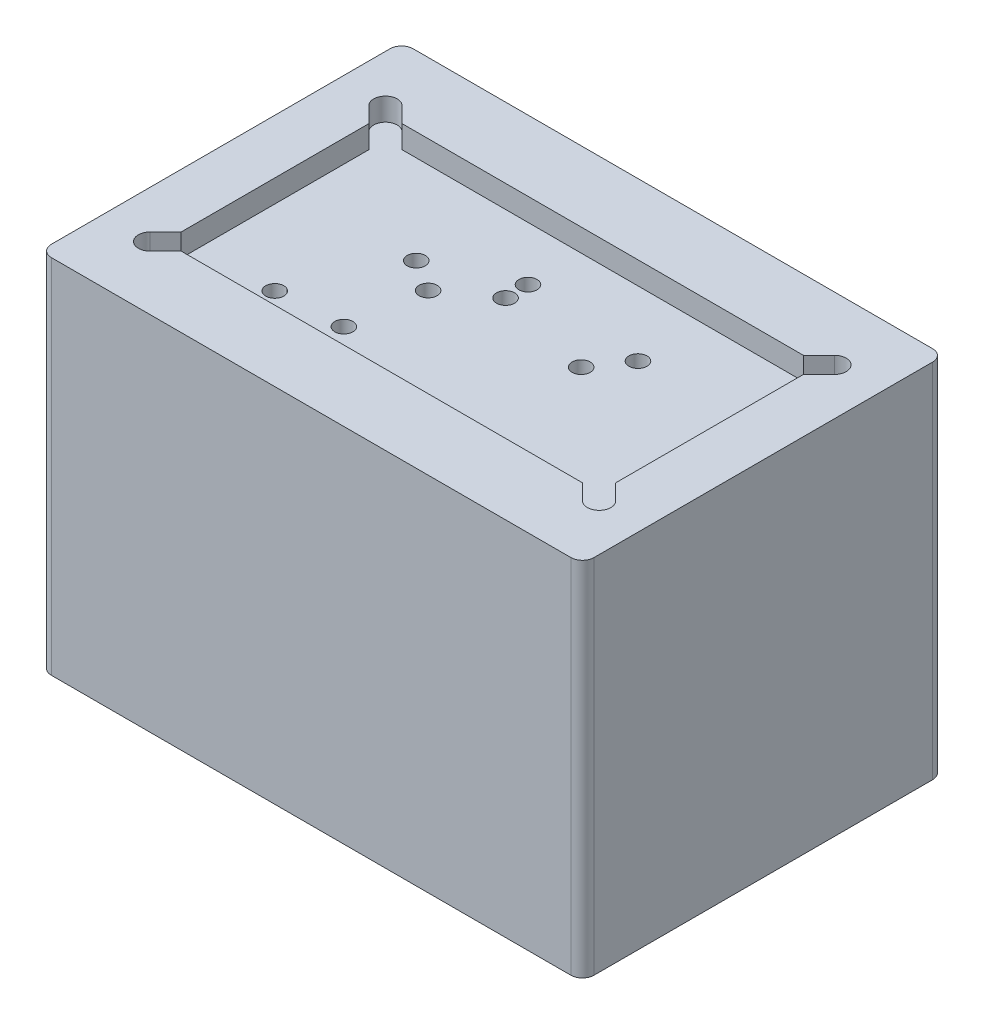
SolidWorks part; units mm, degrees
ref_plane "Front" through (0, 0, 0) normal (0, 0, 1) x (1, 0, 0)
ref_plane "Top" through (0, 0, 0) normal (0, 1, 0) x (1, 0, 0)
ref_plane "Right" through (0, 0, 0) normal (1, 0, 0) x (0, 0, -1)
sketch "Sketch1" plane through (0, 0, 0) normal (0, 1, 0) x (1, 0, 0)
  line L0 (-19.05, -12.7) -> (19.05, 12.7) construction
  line L1 (-19.05, 12.7) -> (19.05, 12.7)
  line L2 (-19.05, 12.7) -> (-19.05, -12.7)
  line L3 (-19.05, -12.7) -> (19.05, -12.7)
  line L4 (19.05, 12.7) -> (19.05, -12.7)
  point P4 (0, 0)
  dimension "D1" = 38.1
  dimension "D2" = 25.4
extrude "Boss-Extrude1" add sketch "Sketch1" along normal blind 25.4
sketch "Sketch3" plane through (0, 0, 0) normal (0, -1, 0) x (1, 0, 0)
  line L0 (-14.986, -7.5057) -> (15.014, -7.5057)
  line L1 (15.014, -7.5057) -> (15.014, 7.4943)
  line L2 (15.014, 7.4943) -> (-14.986, 7.4943)
  line L3 (-14.986, 7.4943) -> (-14.986, -7.5057)
  arc A0 (15.014, -7.5057) -> (15.014, -7.4993) centre (15.014, -7.5025) ccw
  arc A1 (-14.986, -7.5057) -> (-14.986, -7.512) centre (-14.986, -7.5089) ccw
  arc A2 (15.014, 7.4943) -> (15.0076, 7.4943) centre (15.0108, 7.4943) ccw
  arc A3 (15.014, -7.5057) -> (15.0203, -7.5057) centre (15.0172, -7.5057) ccw
  arc A4 (-14.986, 7.4943) -> (-14.986, 7.4879) centre (-14.986, 7.4911) ccw
  arc A5 (15.014, 7.4943) -> (15.014, 7.5006) centre (15.014, 7.4975) ccw
  arc A6 (-14.986, -7.5057) -> (-14.9796, -7.5057) centre (-14.9828, -7.5057) ccw
  arc A7 (-14.986, 7.4943) -> (-14.9923, 7.4943) centre (-14.9892, 7.4943) ccw
  circle A8 centre (-13.081, 5.5753) radius 1.1303
  circle A9 centre (13.1064, -5.6007) radius 1.1303
  circle A10 centre (-6.8326, -1.5113) radius 0.3175
  circle A11 centre (-9.9568, 5.2959) radius 0.3175
  circle A12 centre (-4.5974, -0.1143) radius 0.3175
  circle A13 centre (5.4356, -0.8255) radius 0.3175
  circle A14 centre (7.0612, -3.1877) radius 0.3175
  circle A15 centre (-1.4224, -2.3749) radius 0.3175
  circle A16 centre (-5.3594, 5.0419) radius 0.3175
  circle A17 centre (-1.4478, -3.9751) radius 0.3175
sketch "Sketch4" plane through (0, 25.4, 0) normal (0, 1, 0) x (1, 0, 0)
  circle A0 centre (-9.9568, -5.2959) radius 0.635
  circle A1 centre (-5.3594, -5.0419) radius 0.635
  circle A2 centre (-4.5974, 0.1143) radius 0.635
  circle A3 centre (-6.8326, 1.5113) radius 0.635
  circle A4 centre (-1.4478, 3.9751) radius 0.635
  circle A5 centre (-1.4224, 2.3749) radius 0.635
  circle A6 centre (5.4356, 0.8255) radius 0.635
  circle A7 centre (7.0612, 3.1877) radius 0.635
  circle A8 centre (5.4356, 0.8255) radius 0.3175 construction
  circle A9 centre (-9.9568, -5.2959) radius 0.3175 construction
  circle A10 centre (-5.3594, -5.0419) radius 0.3175 construction
  circle A11 centre (-4.5974, 0.1143) radius 0.3175 construction
  circle A12 centre (-6.8326, 1.5113) radius 0.3175 construction
  circle A13 centre (-1.4478, 3.9751) radius 0.3175 construction
  circle A14 centre (-1.4224, 2.3749) radius 0.3175 construction
  circle A15 centre (7.0612, 3.1877) radius 0.3175 construction
  dimension "D1" = 1.27
extrude "Cut-Extrude1" cut sketch "Sketch4" against normal through all
sketch "Sketch5" plane through (0, 25.4, 0) normal (0, 1, 0) x (1, 0, 0)
  line L4 (-15.1643, 8.8514) -> (-14.0726, 7.7597)
  line L5 (-16.3317, 7.684) -> (-15.24, 6.5923)
  line L6 (15.1923, 8.8514) -> (14.1006, 7.7597)
  line L7 (16.3597, 7.684) -> (15.268, 6.5923)
  line L8 (-15.24, 7.7597) -> (-15.24, -7.7483)
  line L9 (-15.24, -7.7483) -> (15.268, -7.7483)
  line L10 (15.268, -7.7483) -> (15.268, 7.7597)
  line L11 (15.268, 7.7597) -> (-15.24, 7.7597)
  line L12 (-15.24, 6.5923) -> (-15.24, -6.5809)
  line L13 (-14.0726, -7.7483) -> (14.1006, -7.7483)
  line L14 (15.268, -6.5809) -> (15.268, 6.5923)
  line L15 (14.1006, 7.7597) -> (-14.0726, 7.7597)
  line L16 (15.1923, -8.84) -> (14.1006, -7.7483)
  line L17 (16.3597, -7.6726) -> (15.268, -6.5809)
  line L18 (-16.3317, -7.6726) -> (-15.24, -6.5809)
  line L19 (-15.1643, -8.84) -> (-14.0726, -7.7483)
  arc A0 (-15.1643, 8.8514) -> (-16.3317, 7.684) centre (-15.748, 8.2677) ccw
  arc A1 (-16.3317, -7.6726) -> (-15.1643, -8.84) centre (-15.748, -8.2563) ccw
  arc A2 (15.1923, -8.84) -> (16.3597, -7.6726) centre (15.776, -8.2563) ccw
  arc A3 (16.3597, 7.684) -> (15.1923, 8.8514) centre (15.776, 8.2677) ccw
  dimension "D2" = 1.651
  dimension "D3" = 0.508
  dimension "D4" = 0.508
  dimension "D5" = 0.508
  dimension "D6" = 0.508
  dimension "D1" = 0.254
extrude "Cut-Extrude2" cut sketch "Sketch5" against normal blind 1.5875
sketch "Sketch6" plane through (0, 0, 0) normal (0, -1, 0) x (1, 0, 0)
  line L4 (-19.05, -12.7) -> (-19.05, 12.7) construction
  line L5 (-19.05, -3.175) -> (-19.05, 3.175)
  line L6 (-19.05, 3.175) -> (-16.51, 3.175)
  line L7 (-16.51, -3.175) -> (-19.05, -3.175)
  line L8 (-16.51, -10.16) -> (16.51, -10.16)
  line L9 (-16.51, 10.16) -> (-16.51, -10.16)
  line L10 (16.51, -10.16) -> (16.51, 10.16)
  line L11 (16.51, 10.16) -> (-16.51, 10.16)
  line L12 (-16.51, -10.16) -> (16.51, -10.16)
  line L13 (-16.51, 10.16) -> (-16.51, 3.175)
  line L14 (16.51, -10.16) -> (16.51, 10.16)
  line L15 (16.51, 10.16) -> (-16.51, 10.16)
  line L16 (-16.51, -3.175) -> (-16.51, -10.16)
  dimension "D2" = 6.35
  dimension "D3" = 3.175
  dimension "D1" = 2.54
extrude "Cut-Extrude3" cut sketch "Sketch6" against normal blind 3.175
fillet "Fillet1" radius 3.302 4 edges at (-16.51, 1.5875, -10.16) (16.51, 1.5875, -10.16) (16.51, 1.5875, 10.16) (-16.51, 1.5875, 10.16)
fillet "Fillet2" radius 0.8128 6 edges at (-19.05, 12.7, -12.7) (19.05, 12.7, -12.7) (19.05, 12.7, 12.7) (-19.05, 12.7, 12.7) (-16.51, 1.5875, -3.175) (-16.51, 1.5875, 3.175)
chamfer "Chamfer1" distance 0.635 angle 45 8 edges at (7.0612, 3.175, -2.5527) (5.4356, 3.175, -0.1905) (-1.4478, 3.175, -3.3401) (-1.4224, 3.175, -1.7399) (-4.5974, 3.175, 0.5207) (-6.8326, 3.175, -0.8763) (-5.3594, 3.175, 5.6769) (-9.9568, 3.175, 5.9309)
